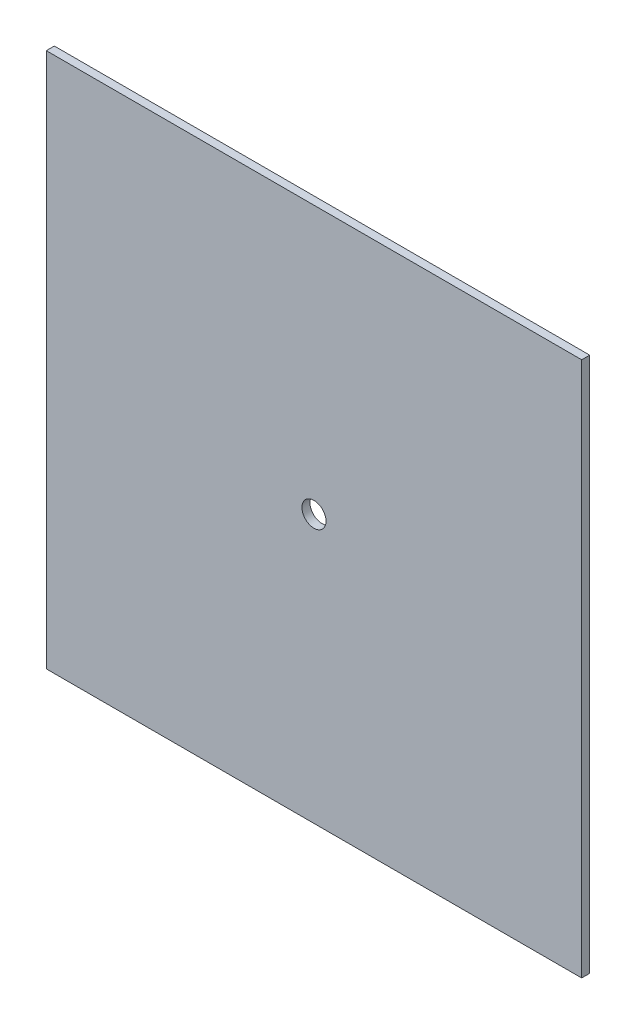
SolidWorks part; units mm, degrees
ref_plane "Front Plane" through (0, 0, 0) normal (0, 0, 1) x (1, 0, 0)
ref_plane "Top Plane" through (0, 0, 0) normal (0, 1, 0) x (1, 0, 0)
ref_plane "Right Plane" through (0, 0, 0) normal (1, 0, 0) x (0, 0, -1)
sketch "Baseplate" plane through (0, 0, 0) normal (0, 0, 1) x (1, 0, 0)
  line L2 (-100, 100) -> (100, 100)
  line L3 (-100, 100) -> (-100, -100)
  line L4 (-100, -100) -> (100, -100)
  line L5 (100, 100) -> (100, -100)
  line L6 (-100, 100) -> (100, -100) construction
  line L7 (-100, -100) -> (100, 100) construction
  point P2 (0, 0)
  dimension "D1" = 200
  dimension "D2" = 200
extrude "Boss-Extrude1" add sketch "Baseplate" along normal blind 3
sketch "Sketch3" plane through (0, 0, 3) normal (0, 0, 1) x (1, 0, 0)
  circle A0 centre (0, 0) radius 4.5
  point P3 (0, 0)
  dimension "D1" = 9
extrude "Cut-Extrude1" cut sketch "Sketch3" against normal blind 3
